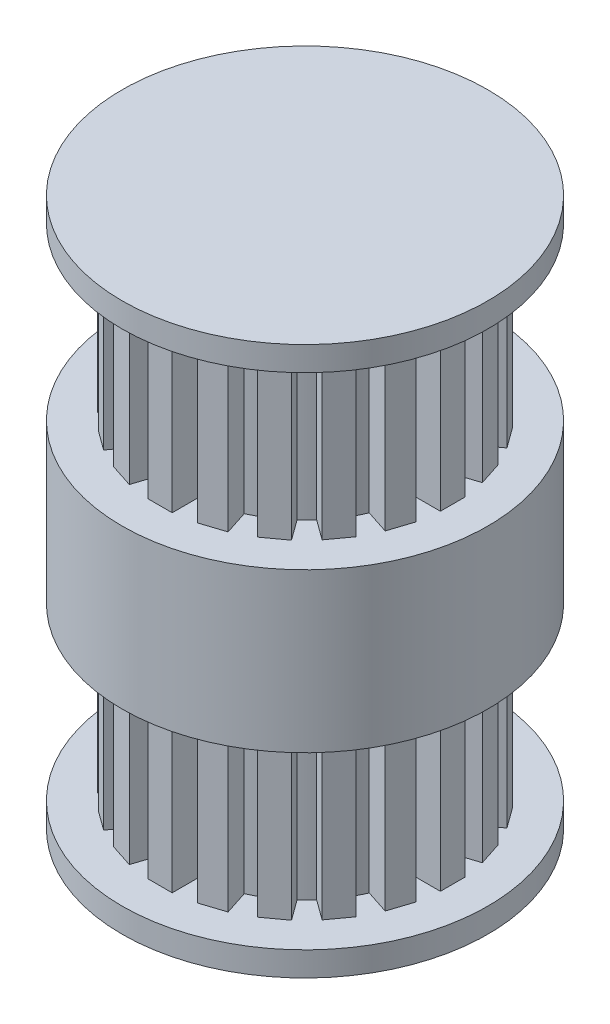
SolidWorks part; units mm, degrees
ref_plane "Ön Düzlem" through (0, 0, 0) normal (0, 0, 1) x (1, 0, 0)
ref_plane "Üst Düzlem" through (0, 0, 0) normal (0, 1, 0) x (1, 0, 0)
ref_plane "Sağ Düzlem" through (0, 0, 0) normal (1, 0, 0) x (0, 0, -1)
sketch "Çizim1" plane through (0, 0, 0) normal (0, 1, 0) x (1, 0, 0)
  circle A0 centre (0, 0) radius 7.5
extrude "Yükseklik-Ekstrüzyon1" add sketch "Çizim1" along normal blind 6.5
sketch "Çizim6" plane through (0, 6.5, 0) normal (0, 1, 0) x (1, 0, 0)
  circle A0 centre (0, 0) radius 5
extrude "Yükseklik-Ekstrüzyon5" add sketch "Çizim6" along normal blind 7
sketch "Çizim7" plane through (0, 13.5, 0) normal (0, 1, 0) x (1, 0, 0)
  line L0 (0, 5) -> (0, 6)
  line L1 (0, 6) -> (0.4468, 6)
  line L2 (0.4468, 6) -> (0.4468, 4.4288)
  line L3 (0.4468, 4.4288) -> (-0.5532, 4.4288)
  line L4 (-0.5532, 4.4288) -> (-0.5532, 6)
  line L5 (-0.5532, 6) -> (0, 6)
  circle A0 centre (0, 0) radius 5 construction
  circle A1 centre (0, 0) radius 5 construction
  circle M3 centre (0, 0) radius 5
extrude "Yükseklik-Ekstrüzyon6" add sketch "Çizim7" against normal blind 7 contours L2 L1 L0 M3 | L5 L4 L0 M3 region at (-0.278, 13.5, -5.4948) region at (0.2241, 13.5, -5.4967)
pattern_circular "Dairesel Kaplama2" count 20 over 360 about axis through (0, 13.5, 0) along (0, 1, 0) of "Yükseklik-Ekstrüzyon6"
sketch "Çizim8" plane through (0, 13.5, 0) normal (0, 1, 0) x (1, 0, 0)
  circle A0 centre (0, 0) radius 7.5
extrude "Yükseklik-Ekstrüzyon7" add sketch "Çizim8" along normal blind 1
sketch "Çizim9" plane through (0, 14.5, 0) normal (0, 1, 0) x (1, 0, 0)
  circle A0 centre (0, 0) radius 8
extrude "Kes-Ekstrüzyon2" cut sketch "Çizim9" against normal blind 15 rebuild error yes
sketch "Çizim10" plane through (0, 0, 0) normal (1, 0, 0) x (0, 0, -1)
  circle A0 centre (0, 2.3612) radius 1.2
extrude "Kes-Ekstrüzyon3" cut sketch "Çizim10" against normal blind 21
ref_plane "Düzlem1" through (0, 3.25, 0) normal (0, -1, 0) x (-1, 0, 0)
mirror "Aynalama1" about plane through (0, 3.25, 0) normal (0, -1, 0) of "Yükseklik-Ekstrüzyon7", "Dairesel Kaplama2", "Yükseklik-Ekstrüzyon6"
mirror "Aynalama2" about plane through (0, 3.25, 0) normal (0, -1, 0) of "Yükseklik-Ekstrüzyon5"
mirror "Aynalama4" about plane through (0, 3.25, 0) normal (0, -1, 0) rebuild error yes
